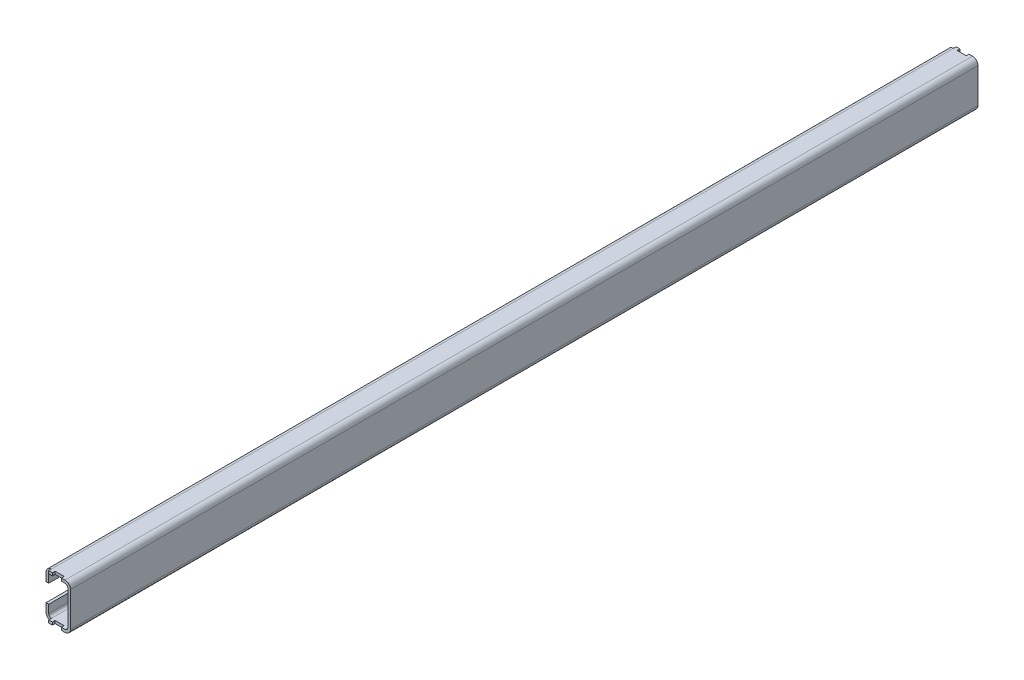
SolidWorks part; units mm, degrees
ref_plane "Front Plane" through (0, 0, 0) normal (0, 0, 1) x (1, 0, 0)
ref_plane "Top Plane" through (0, 0, 0) normal (0, 1, 0) x (1, 0, 0)
ref_plane "Right Plane" through (0, 0, 0) normal (1, 0, 0) x (0, 0, -1)
sketch "Sketch1" plane through (0, 0, 0) normal (0, 0, 1) x (1, 0, 0)
  line L0 (0, 0) -> (30, 0)
  line L1 (30, 0) -> (30, 50)
  line L2 (30, 50) -> (0, 50)
  line L6 (0, 50) -> (0, 35)
  line L7 (0, 15) -> (0, 0)
  line L8 (3, 15) -> (3, 3)
  line L9 (3, 3) -> (27, 3)
  line L10 (27, 3) -> (27, 47)
  line L11 (27, 47) -> (3, 47)
  line L12 (3, 47) -> (3, 35)
  line L13 (0, 35) -> (3, 35)
  line L14 (3, 15) -> (0, 15)
  dimension "D1" = 30
  dimension "D2" = 50
  dimension "D3" = 15
  dimension "D5" = 3
extrude "Boss-Extrude1" add sketch "Sketch1" along normal mid plane 1000
fillet "Fillet1" radius 6 4 edges at (30, 0, 0) (30, 50, 0) (0, 0, 0) (0, 50, 0)
fillet "Fillet2" radius 3 4 edges at (27, 47, 0) (3, 47, 0) (3, 3, 0) (27, 3, 0)
sketch "Sketch2" plane through (0, 50, 0) normal (0, 1, 0) x (1, 0, 0)
  line L0 (24, 500) -> (6, 500) construction
  line L1 (10, 500) -> (20, 500)
  line L2 (10, 500) -> (10, 497)
  line L3 (10, 497) -> (20, 497)
  line L4 (20, 500) -> (20, 497)
  line L5 (0, 0) -> (159.7054, 0) construction
  line L10 (0, -500) -> (0, 500) construction
  line L11 (6, 500) -> (0, 500)
  line L12 (6, 500) -> (6, 497)
  line L13 (6, 497) -> (0, 497)
  line L14 (0, 500) -> (0, 497)
  line L15 (0, -500) -> (0, -497)
  line L16 (6, -497) -> (0, -497)
  line L17 (6, -500) -> (6, -497)
  line L18 (6, -500) -> (0, -500)
  line L19 (20, -500) -> (20, -497)
  line L20 (10, -497) -> (20, -497)
  line L21 (10, -500) -> (10, -497)
  line L22 (10, -500) -> (20, -500)
  dimension "D1" = 3
  dimension "D2" = 10
  dimension "D3" = 10
extrude "Cut-Extrude1" cut sketch "Sketch2" against normal up to surface (50 mm away) up to face at (15, 0, 0)
